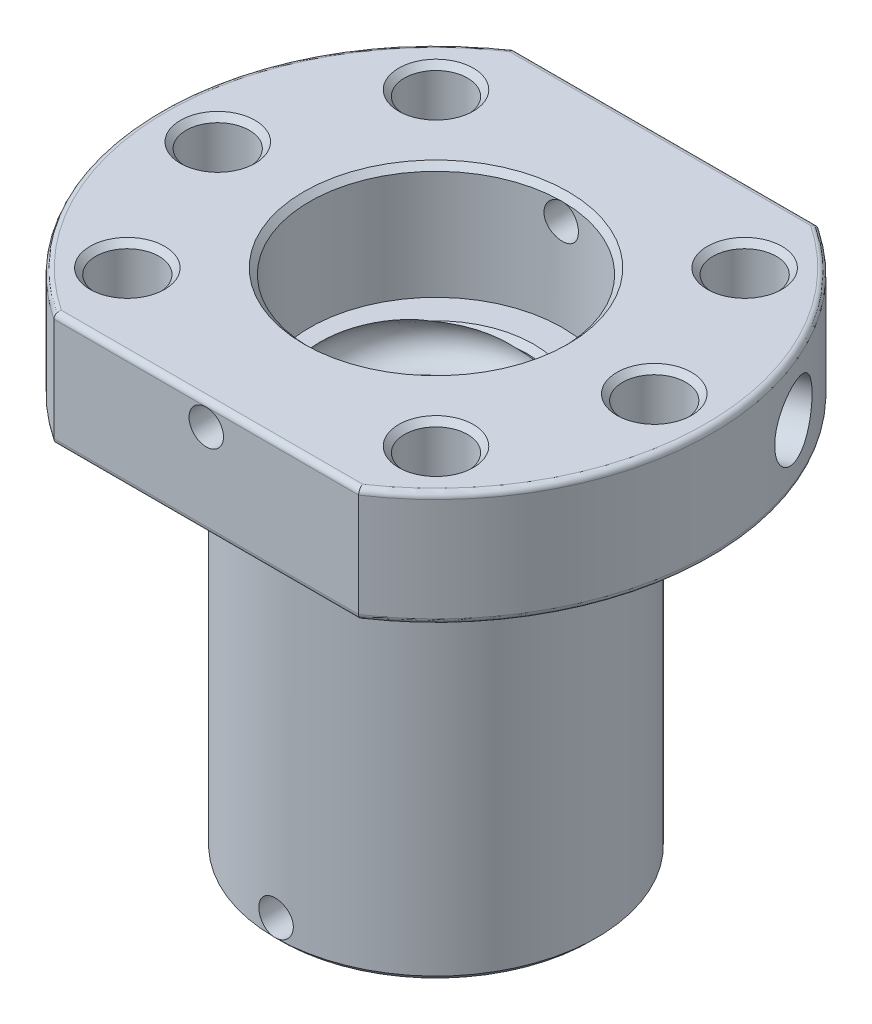
SolidWorks part; units mm, degrees
ref_plane "Front Plane" through (0, 0, 0) normal (0, 0, 1) x (1, 0, 0)
ref_plane "Top Plane" through (0, 0, 0) normal (0, 1, 0) x (1, 0, 0)
ref_plane "Right Plane" through (0, 0, 0) normal (1, 0, 0) x (0, 0, -1)
sketch "Sketch1" plane through (0, 0, 0) normal (1, 0, 0) x (0, 0, -1)
  line L0 (0, 0) -> (0, -44) construction
  line L1 (0, 0) -> (-24, 0) construction
  line L2 (-24, 0) -> (-24, -44) construction
  line L3 (-24, -44) -> (0, -44) construction
  line L4 (-14, 0) -> (-14, -44) construction
  line L5 (-24, -10) -> (0, -10) construction
  line L6 (-11, 0) -> (-11, -44) construction
  line L7 (-11, 0) -> (-24, 0)
  line L8 (-24, 0) -> (-24, -10)
  line L9 (-24, -10) -> (-14, -10)
  line L10 (-14, -10) -> (-14, -44)
  line L11 (-14, -44) -> (-11, -44)
  line L12 (-11, -44) -> (-11, -34)
  line L13 (-8, 0) -> (-8, -44) construction
  line L14 (-14, -10) -> (0, -10) construction
  line L15 (0, -22) -> (-14, -22) construction
  line L16 (-14, -34) -> (0, -34) construction
  line L17 (-11, -10) -> (-8, -10)
  line L18 (-8, -10) -> (-8, -34)
  line L19 (-8, -34) -> (-11, -34)
  line L20 (-11, -10) -> (-11, 0)
  dimension "D1" = 44
  dimension "D2" = 24
  dimension "D3" = 14
  dimension "D4" = 10
  dimension "D5" = 11
  dimension "D6" = 8
  dimension "D7" = 10
revolve "Revolve1" add sketch "Sketch1" angle 360 about L0
sketch "Sketch2" plane through (0, 0, 0) normal (0, 1, 0) x (1, 0, 0)
  line L1 (-20, 20) -> (20, 20) construction
  line L2 (-20, 20) -> (-20, -20) construction
  line L3 (-20, -20) -> (20, -20) construction
  line L4 (20, 20) -> (20, -20) construction
  line L5 (-20, 20) -> (20, -20) construction
  line L6 (-20, -20) -> (20, 20) construction
  line L7 (-13.2665, 20) -> (13.2665, 20)
  line L9 (-13.2665, -20) -> (13.2665, -20)
  line L11 (-20, 20) -> (20, -20) construction
  line L12 (-20, -20) -> (20, 20) construction
  circle A0 centre (0, 0) radius 24 construction
  arc A1 (-13.2665, -20) -> (13.2665, -20) centre (0, 0) ccw
  arc A3 (13.2665, 20) -> (-13.2665, 20) centre (0, 0) ccw
  dimension "D2" = 48
  dimension "D1" = 40
extrude "Cut-Extrude2" cut sketch "Sketch2" against normal up to next
sketch "Sketch3" plane through (0, 0, 0) normal (0, 0, 1) x (1, 0, 0)
  line L0 (0, 0) -> (0, -44) construction
  line L1 (-14, -44) -> (14, -44) construction
ref_axis "Axis1" through (0, 0, 0) along (0, -1, 0)
sketch "Sketch4" plane through (0, 0, 0) normal (0, 1, 0) x (1, 0, 0)
  line L0 (-24, 0) -> (24, 0) construction
  line L1 (-13.435, -13.435) -> (0, 0) construction
  line L2 (0, 20) -> (0, -20) construction
  line L3 (-13.2665, 20) -> (13.2665, 20) construction
  line L4 (13.2665, -20) -> (-13.2665, -20) construction
  arc A0 (-13.2665, 20) -> (-13.2665, -20) centre (0, 0) ccw construction
  arc A1 (13.2665, -20) -> (13.2665, 20) centre (0, 0) ccw construction
  circle A2 centre (-19, 0) radius 2.75
  circle A3 centre (0, 0) radius 19 construction
  circle A4 centre (-13.435, -13.435) radius 2.75
  circle A5 centre (-13.435, 13.435) radius 2.75
  circle A6 centre (13.435, -13.435) radius 2.75
  circle A7 centre (19, 0) radius 2.75
  circle A8 centre (13.435, 13.435) radius 2.75
  dimension "D2" = 5.5
  dimension "D1" = 19
  dimension "D3" = 45
extrude "Cut-Extrude3" cut sketch "Sketch4" against normal up to next
chamfer "Chamfer1" distance 0.5 angle 45 17 edges at (13.435, -10, -16.185) (-13.435, -10, -16.185) (-19, -10, -2.75) (-13.435, -10, 10.685) (13.435, -10, 10.685) (19, -10, -2.75) (0, -44, 11) (0, -44, 14) (-19, 0, 2.75) (-13.435, 0, 16.185) (13.435, 0, 10.685) (19, 0, -2.75) (13.435, 0, -10.685) (-13.435, 0, -16.185) (0, -10, 8) (0, -34, 8) (0, 0, 11)
ref_plane "Plane1" through (22.1731, 0, -9.1844) normal (0.9239, 0, -0.3827) x (-0.3827, 0, -0.9239)
sketch "Sketch5" plane through (22.1731, 0, -9.1844) normal (0.9239, 0, -0.3827) x (-0.3827, 0, -0.9239)
  line L0 (0, 0) -> (0, -10.0004) construction
  line L1 (0, 0) -> (0, -44) construction
  circle A0 centre (0, -5.0002) radius 2.5
  dimension "D1" = 5
extrude "Cut-Extrude4" cut sketch "Sketch5" against normal up to next
sketch "Sketch6" plane through (22.1731, 0, -9.1844) normal (0.9239, 0, -0.3827) x (-0.3827, 0, -0.9239)
  circle A0 centre (0, -5.0002) radius 3
  dimension "D1" = 6
extrude "Cut-Extrude5" cut sketch "Sketch6" against normal blind 10
fillet "Fillet1" radius 0.5 9 edges at (0, -10, 14) (0, -10, 20) (-24, -10, 0) (0, -10, -20) (24, -10, 0) (24, 0, 0) (0, 0, 20) (-24, 0, 0) (0, 0, -20)
ref_plane "Plane2" through (0, 0, 20) normal (0, 0, 1) x (1, 0, 0)
sketch "Sketch7" plane through (0, 0, 20) normal (0, 0, 1) x (1, 0, 0)
  line L0 (0, 0) -> (0, -44) construction
  circle A0 centre (0, -2) radius 1.5
  dimension "D1" = 3
  dimension "D2" = 2
extrude "Cut-Extrude6" cut sketch "Sketch7" against normal through all
ref_plane "Plane3" through (0, 0, 14) normal (0, 0, 1) x (1, 0, 0)
sketch "Sketch8" plane through (0, 0, 14) normal (0, 0, 1) x (1, 0, 0)
  line L0 (0, 0) -> (0, -44) construction
  circle A0 centre (0, -42) radius 1.5
  dimension "D1" = 3
  dimension "D2" = 2
extrude "Cut-Extrude7" cut sketch "Sketch8" against normal blind 28
sketch "Sketch9" plane through (0, 0, 0) normal (0, 1, 0) x (1, 0, 0)
  circle A0 centre (0, 0) radius 8
curve "Helix/Spiral1" pitch 5 height 44 radius 8 centre (0, 0, 0) axis (0, -1, 0) start towards (0, 0, 1)
sketch "Sketch10" plane through (0, 0, 0) normal (1, 0, 0) x (0, 0, -1)
  circle A0 centre (-8, 0) radius 1.9
  spline S0 degree 3 poles (-8, 0) (-8, -0.1041) (-7.5786, -0.3146) (-5.7797, -0.6285) (-3.091, -0.9429) (0.0737, -1.2571) (3.227, -1.5714) (5.8835, -1.8857) (7.6341, -2.2) (8.2094, -2.5143) (7.5207, -2.8286) (5.6741, -3.1429) (2.9539, -3.4571) (-0.2211, -3.7714) (-3.362, -4.0857) (-5.9853, -4.4) (-7.6871, -4.7143) (-8.2054, -5.0286) (-7.4603, -5.3429) (-5.5667, -5.6571) (-2.8159, -5.9714) (0.3684, -6.2857) (3.4959, -6.6) (6.0853, -6.9143) (7.7377, -7.2286) (8.1988, -7.5429) (7.3976, -7.8571) (5.4574, -8.1714) (2.677, -8.4857) (-0.5156, -8.8) (-3.6287, -9.1143) (-6.1832, -9.4286) (-7.7857, -9.7429) (-8.1895, -10.0571) (-7.3324, -10.3714) (-5.3464, -10.6857) (-2.5372, -11) (0.6626, -11.3143) (3.7604, -11.6286) (6.2792, -11.9429) (7.8313, -12.2571) (8.1776, -12.5714) (7.2649, -12.8857) (5.2337, -13.2) (2.3967, -13.5143) (-0.8094, -13.8286) (-3.8908, -14.1429) (-6.3732, -14.4571) (-7.8743, -14.7714) (-8.1631, -15.0857) (-7.1951, -15.4) (-5.1193, -15.7143) (-2.2553, -16.0286) (0.9559, -16.3429) (4.02, -16.6571) (6.4651, -16.9714) (7.9148, -17.2857) (8.1459, -17.6) (7.1229, -17.9143) (5.0032, -18.2286) (2.1132, -18.5429) (-1.1021, -18.8571) (-4.1478, -19.1714) (-6.5549, -19.4857) (-7.9527, -19.8) (-8.1262, -20.1143) (-7.0485, -20.4286) (-4.8856, -20.7429) (-1.9705, -21.0571) (1.248, -21.3714) (4.2744, -21.6857) (6.6426, -22) (7.9881, -22.3143) (8.1038, -22.6286) (6.9717, -22.9429) (4.7663, -23.2571) (1.8271, -23.5714) (-1.3935, -23.8857) (-4.3995, -24.2) (-6.7282, -24.5143) (-8.0209, -24.8286) (-8.0787, -25.1429) (-6.8927, -25.4571) (-4.6455, -25.7714) (-1.6831, -26.0857) (1.5385, -26.4) (4.5232, -26.7143) (6.8115, -27.0286) (8.0511, -27.3429) (8.0511, -27.6571) (6.8115, -27.9714) (4.5232, -28.2857) (1.5385, -28.6) (-1.6831, -28.9143) (-4.6455, -29.2286) (-6.8927, -29.5429) (-8.0787, -29.8571) (-8.0209, -30.1714) (-6.7282, -30.4857) (-4.3995, -30.8) (-1.3935, -31.1143) (1.8271, -31.4286) (4.7663, -31.7429) (6.9717, -32.0571) (8.1038, -32.3714) (7.9881, -32.6857) (6.6426, -33) (4.2744, -33.3143) (1.248, -33.6286) (-1.9705, -33.9429) (-4.8856, -34.2571) (-7.0485, -34.5714) (-8.1262, -34.8857) (-7.9527, -35.2) (-6.5549, -35.5143) (-4.1478, -35.8286) (-1.1021, -36.1429) (2.1132, -36.4571) (5.0032, -36.7714) (7.1229, -37.0857) (8.1459, -37.4) (7.9148, -37.7143) (6.4651, -38.0286) (4.02, -38.3429) (0.9559, -38.6571) (-2.2553, -38.9714) (-5.1193, -39.2857) (-7.1951, -39.6) (-8.1631, -39.9143) (-7.8743, -40.2286) (-6.3732, -40.5429) (-3.8908, -40.8571) (-0.8094, -41.1714) (2.3967, -41.4857) (5.2337, -41.8) (7.2649, -42.1143) (8.1777, -42.4286) (7.8312, -42.7429) (6.2794, -43.0571) (3.7596, -43.3715) (0.6655, -43.6854) (-1.4769, -43.8959) (-2.4721, -44) knots 0 0 0 0 0.007143 0.014286 0.021429 0.028571 0.035714 0.042857 0.05 0.057143 0.064286 0.071429 0.078571 0.085714 0.092857 0.1 0.107143 0.114286 0.121429 0.128571 0.135714 0.142857 0.15 0.157143 0.164286 0.171429 0.178571 0.185714 0.192857 0.2 0.207143 0.214286 0.221429 0.228571 0.235714 0.242857 0.25 0.257143 0.264286 0.271429 0.278571 0.285714 0.292857 0.3 0.307143 0.314286 0.321429 0.328571 0.335714 0.342857 0.35 0.357143 0.364286 0.371429 0.378571 0.385714 0.392857 0.4 0.407143 0.414286 0.421429 0.428571 0.435714 0.442857 0.45 0.457143 0.464286 0.471429 0.478571 0.485714 0.492857 0.5 0.507143 0.514286 0.521429 0.528571 0.535714 0.542857 0.55 0.557143 0.564286 0.571429 0.578571 0.585714 0.592857 0.6 0.607143 0.614286 0.621429 0.628571 0.635714 0.642857 0.65 0.657143 0.664286 0.671429 0.678571 0.685714 0.692857 0.7 0.707143 0.714286 0.721429 0.728571 0.735714 0.742857 0.75 0.757143 0.764286 0.771429 0.778571 0.785714 0.792857 0.8 0.807143 0.814286 0.821429 0.828571 0.835714 0.842857 0.85 0.857143 0.864286 0.871429 0.878571 0.885714 0.892857 0.9 0.907143 0.914286 0.921429 0.928571 0.935714 0.942857 0.95 0.957143 0.964286 0.971429 0.978571 0.985714 0.992857 1 1 1 1 construction
  dimension "D1" = 3.8
sweep "Cut-Sweep1" cut profiles "Sketch10" path "Helix/Spiral1"
